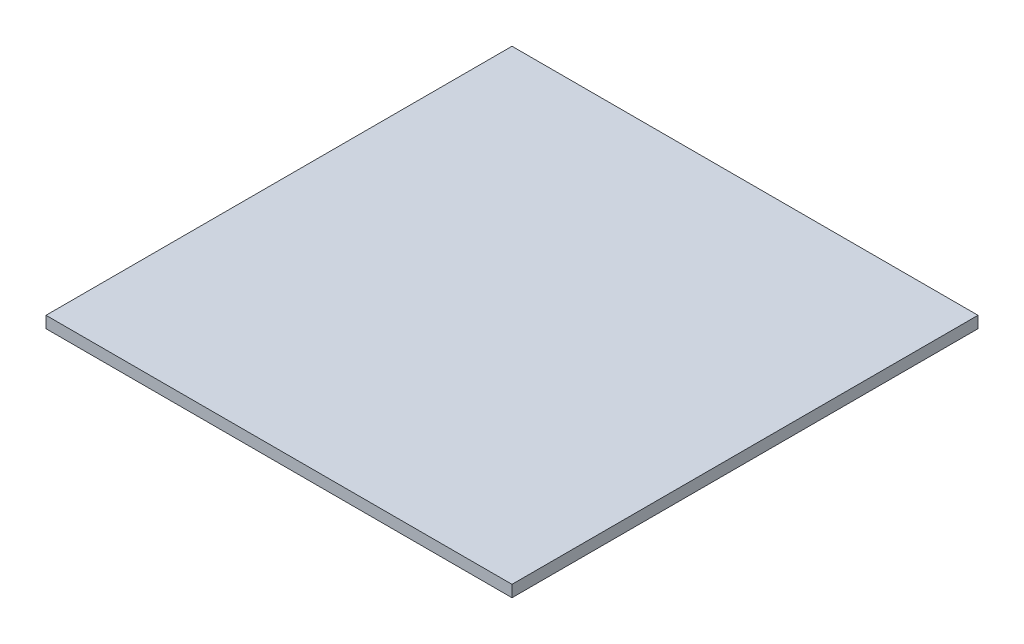
SolidWorks part; units mm, degrees
material "Balsa"
ref_plane "Plano frontal" through (0, 0, 0) normal (0, 0, 1) x (1, 0, 0)
ref_plane "Plano superior" through (0, 0, 0) normal (0, 1, 0) x (1, 0, 0)
ref_plane "Plano direito" through (0, 0, 0) normal (1, 0, 0) x (0, 0, -1)
sketch "Esboço1" plane through (0, 0, 0) normal (0, 1, 0) x (1, 0, 0)
  line L1 (-300, -300) -> (300, -300)
  line L2 (-300, -300) -> (-300, 300)
  line L3 (-300, 300) -> (300, 300)
  line L4 (300, -300) -> (300, 300)
  line L5 (-300, -300) -> (300, 300) construction
  line L6 (-300, 300) -> (300, -300) construction
  point P0 (0, 0)
  dimension "D1" = 600
  dimension "D2" = 600
extrude "Ressalto-extrusão1" add sketch "Esboço1" along normal blind 15
